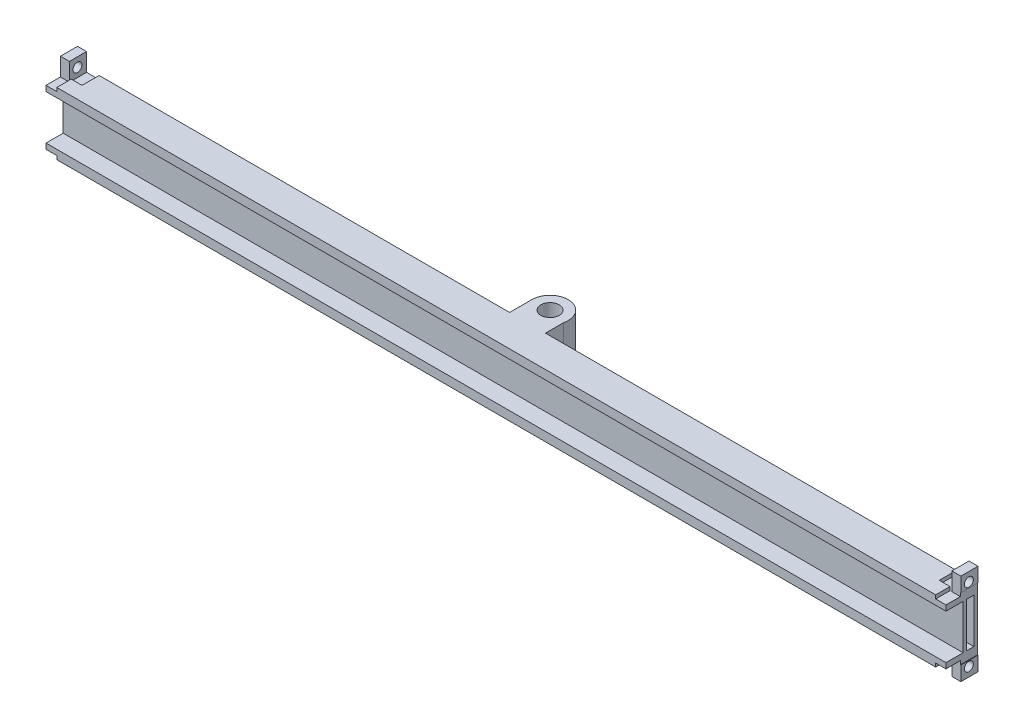
SolidWorks part; units mm, degrees
material "PLA"
ref_plane "Front Plane" through (0, 0, 0) normal (1, 0, 0) x (0, 1, 0)
ref_plane "Top Plane" through (0, 0, 0) normal (0, 0, 1) x (0, 1, 0)
ref_plane "Right Plane" through (0, 0, 0) normal (0, 1, 0) x (-1, 0, 0)
sketch "Sketch1" plane through (0, 0, 0) normal (1, 0, 0) x (0, 1, 0)
  line L16 (0, 4.7625) -> (-2.5, 4.7625)
  line L17 (0, 0) -> (12.3825, 0)
  line L18 (0, 0) -> (0, 4.7625)
  line L19 (0, 4.7625) -> (12.3825, 4.7625) construction
  line L20 (12.3825, 0) -> (12.3825, 4.7625)
  line L21 (-2.5, 4.7625) -> (-2.5, -4)
  line L22 (-2.5, -4) -> (14.8825, -4)
  line L23 (14.8825, -4) -> (14.8825, 4.7625)
  line L24 (12.3825, 4.7625) -> (14.8825, 4.7625)
  dimension "D1" = 4.7625
  dimension "D2" = 12.3825
  dimension "D3" = 2.5
extrude "Boss-Extrude1" add sketch "Sketch1" along normal blind 250
sketch "Sketch3" plane through (0, -2.5, 0) normal (0, -1, 0) x (1, 0, 0)
  line L0 (120.0194, -4) -> (129.9806, -4)
  line L1 (250, -4) -> (0, -4) construction
  line L2 (129.9806, -4) -> (129.9806, -9)
  line L3 (120.0194, -4) -> (120.0194, -10.1759)
  line L4 (0, 4.7625) -> (0, -4) construction
  arc A0 (120.0194, -10.1759) -> (129.9806, -9) centre (125.0694, -10.1759) ccw
  circle A1 centre (125.0694, -10.1759) radius 2.55
  point P5 (125, -4)
  dimension "D2" = 5.1
  dimension "D3" = 5
  dimension "D4" = 125
extrude "Boss-Extrude2" add sketch "Sketch3" against normal up to surface (17.3825 mm away) up to face at (125, 14.8825, 0.3813)
sketch "Sketch6" plane through (0, -2.5, 0) normal (0, -1, 0) x (1, 0, 0)
  line L0 (120.0194, -4) -> (0, -4) construction
  line L1 (117.5385, -4) -> (131.3691, -4)
  line L2 (117.5385, -4) -> (117.5385, -13.6365)
  line L3 (117.5385, -13.6365) -> (131.3691, -13.6365)
  line L4 (131.3691, -4) -> (131.3691, -13.6365)
extrude "Cut-Extrude2" [suppressed] cut sketch "Sketch6" against normal blind 5
sketch "Sketch7" plane through (0, 14.8825, 0) normal (0, 1, 0) x (-1, 0, 0)
  line L0 (-250, -4) -> (-129.9806, -4) construction
  line L1 (-136.5723, -4) -> (-116.3235, -4)
  line L2 (-136.5723, -4) -> (-136.5723, -14.7915)
  line L3 (-136.5723, -14.7915) -> (-116.3235, -14.7915)
  line L4 (-116.3235, -4) -> (-116.3235, -14.7915)
extrude "Cut-Extrude3" [suppressed] cut sketch "Sketch7" against normal blind 5
sketch "Sketch8" plane through (250, 0, 0) normal (1, 0, 0) x (0, 1, 0)
  line L0 (6.1913, 0) -> (6.1913, -4) construction
  line L5 (12.3825, 0) -> (0, 0) construction
  line L6 (14.8825, -4) -> (-2.5, -4) construction
  line L11 (0, -3) -> (12.3825, -3)
  line L12 (0, -3) -> (0, -1)
  line L13 (0, -1) -> (12.3825, -1)
  line L14 (12.3825, -3) -> (12.3825, -1)
  line L15 (0, -3) -> (12.3825, -1) construction
  line L16 (0, -1) -> (12.3825, -3) construction
  point P6 (6.1913, -2)
  dimension "D1" = 12.3825
extrude "Cut-Extrude4" cut sketch "Sketch8" against normal through all
sketch "Sketch9" plane through (0, 0, -4) normal (0, 0, -1) x (-1, 0, 0)
  line L0 (-117.5194, -2.5) -> (-117.5194, 14.8825) construction
  line L1 (-120.0194, -2.5) -> (0, -2.5) construction
  line L2 (-120.0194, 14.8825) -> (0, 14.8825) construction
  line L3 (-120.0194, 14.8825) -> (-120.0194, -2.5) construction
  line L4 (-116.5194, 12.3825) -> (-118.5194, 12.3825)
  line L5 (-116.5194, 12.3825) -> (-116.5194, 0)
  line L6 (-116.5194, 0) -> (-118.5194, 0)
  line L7 (-118.5194, 12.3825) -> (-118.5194, 0)
  line L8 (-116.5194, 12.3825) -> (-118.5194, 0) construction
  line L9 (-116.5194, 0) -> (-118.5194, 12.3825) construction
  point P6 (-117.5194, 6.1913)
  dimension "D3" = 2.5
  dimension "D1" = 12.3825
extrude "Cut-Extrude5" cut sketch "Sketch9" against normal up to next
ref_plane "Plane1" through (125.0694, 0, 0) normal (-1, 0, 0) x (0, 0, 1)
mirror "Mirror1" about plane through (125.0694, 0, 0) normal (-1, 0, 0) of "Cut-Extrude5"
sketch "Sketch10" plane through (0, 0, 4.7625) normal (0, 0, 1) x (1, 0, 0)
  line L1 (0, 14.8825) -> (2.5, 14.8825)
  line L2 (0, 14.8825) -> (0, 18.8912)
  line L3 (0, 18.8912) -> (2.5, 18.8912)
  line L4 (2.5, 14.8825) -> (2.5, 18.8912)
  line L5 (0, -2.5) -> (2.5, -2.5)
  line L6 (0, -2.5) -> (0, -6.5088)
  line L7 (0, -6.5088) -> (2.5, -6.5088)
  line L8 (2.5, -2.5) -> (2.5, -6.5088)
  dimension "D2" = 25.4
extrude "Boss-Extrude3" add sketch "Sketch10" against normal up to surface (8.7625 mm away) up to face at (117.5194, 6.1913, -4)
mirror "Mirror2" about plane through (125.0694, 0, 0) normal (-1, 0, 0) of "Boss-Extrude3"
sketch "Sketch11" plane through (250.1388, 0, 0) normal (1, 0, 0) x (0, 1, 0)
  circle A0 centre (16.3513, -1.46) radius 1.25 construction
  circle A1 centre (-3.9687, -1.46) radius 1.25 construction
  circle A2 centre (16.3513, -1.46) radius 1.25
  circle A3 centre (-3.9687, -1.46) radius 1.25
extrude "Cut-Extrude6" cut sketch "Sketch11" against normal up to surface (2.5 mm away) up to face at (247.6388, 16.8869, 0.3813)
mirror "Mirror3" about plane through (125.0694, 0, 0) normal (-1, 0, 0) of "Cut-Extrude6"
sketch "Sketch14" plane through (0, 0, 4.7625) normal (0, 0, 1) x (1, 0, 0)
  line L0 (0, 6.1912) -> (17.1619, 6.1912) construction
  line L1 (0, -6.5088) -> (3, -6.5088)
  line L2 (0, -6.5088) -> (0, -1.5088)
  line L3 (0, -1.5088) -> (3, -1.5088)
  line L4 (3, -6.5088) -> (3, -1.5088)
  line L5 (0, 12.3825) -> (0, 0) construction
  line L6 (0, 13.8912) -> (3, 13.8912)
  line L7 (3, 18.8912) -> (3, 13.8912)
  line L8 (0, 18.8912) -> (3, 18.8912)
  line L9 (0, 18.8912) -> (0, 13.8912)
  dimension "D2" = 3
extrude "Cut-Extrude7" cut sketch "Sketch14" against normal blind 4
mirror "Mirror4" about plane through (125.0694, 0, 0) normal (-1, 0, 0) of "Cut-Extrude7"
sketch "Sketch15" plane through (0, -2.5, 0) normal (0, -1, 0) x (-1, 0, 0)
  line L0 (-3, -0.7625) -> (-2.5, -0.7625) construction
  line L1 (-2.5, 4) -> (-6, 4)
  line L2 (-2.5, 4) -> (-2.5, -0.7625)
  line L3 (-2.5, -0.7625) -> (-6, -0.7625)
  line L4 (-6, 4) -> (-6, -0.7625)
  line L5 (0, 4) -> (0, -0.7625) construction
  dimension "D1" = 6
extrude "Cut-Extrude9" cut sketch "Sketch15" against normal blind 1 contours L4 L3 L2 L1
ref_plane "Plane3" through (0, 6.1913, 0) normal (0, 1, 0) x (1, 0, 0)
mirror "Mirror7" about plane through (0, 6.1913, 0) normal (0, 1, 0) of "Cut-Extrude9"
mirror "Mirror8" about plane through (125.0694, 0, 0) normal (-1, 0, 0) of "Mirror7"
equation "\"D1@Sketch1\"=\"ball_diameter\" * 0.25"
equation "\"D2@Sketch1\"=\"ball_diameter\" * 0.65"
equation "\"D3@Sketch1\"=\"wall_thickness\""
equation "\"D4@Sketch1\"=0.4cm"
equation "\"D1@Boss-Extrude1\"=\"track_length\""
equation "\"D2@Sketch3\"=\"axle\" + 0.01"
equation "\"ball_diameter\"= 0.75in"
equation "\"wall_thickness\" = 0.25cm"
equation "\"track_length\" = 25cm"
equation "\"axle\" = 5mm"
equation "\"D3@Sketch3\"=\"axle\" * 1"
equation "\"D4@Sketch3\"=\"track_length\" / 2"
equation "\"pillar_width\" = 2.75cm"
equation "\"D1@Sketch9\"=\"ball_diameter\" * 0.65"
equation "\"D1@Sketch8\"=\"ball_diameter\"*0.65"
equation "\"D1@Sketch10\"=\"wall_thickness\""
equation "\"D2@Sketch14\"=0.3"
